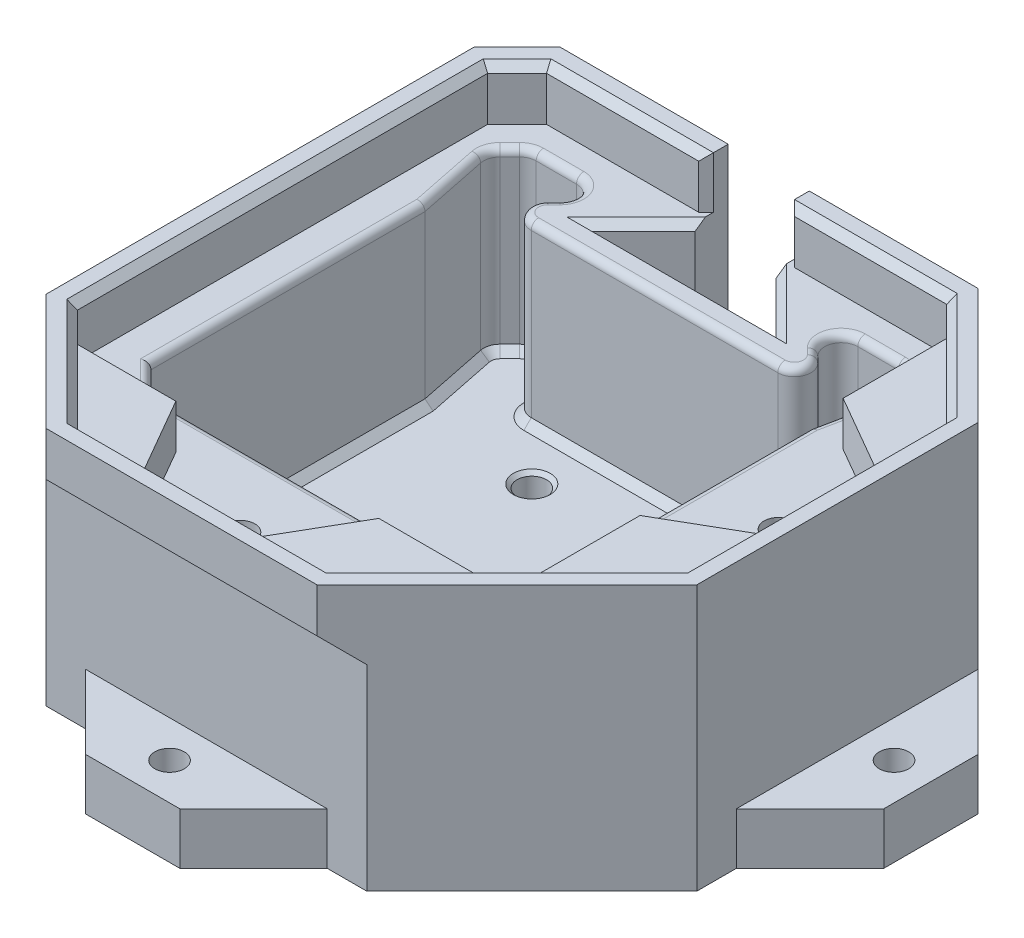
SolidWorks part; units mm, degrees
ref_plane "Front Plane" through (0, 0, 0) normal (0, 0, 1) x (1, 0, 0)
ref_plane "Top Plane" through (0, 0, 0) normal (0, 1, 0) x (1, 0, 0)
ref_plane "Right Plane" through (0, 0, 0) normal (1, 0, 0) x (0, 0, -1)
sketch "Sketch2" plane through (0, 0, 0) normal (0, 1, 0) x (1, 0, 0)
  line L0 (17.15, -41.8374) -> (-17.15, -41.8374)
  line L1 (41.15, -17.8374) -> (41.15, 17.8374)
  line L2 (27.15, 31.8374) -> (-27.15, 31.8374)
  line L3 (-31.15, -27.8374) -> (-31.15, 27.8374)
  line L4 (-17.15, -41.8374) -> (-31.15, -27.8374)
  line L5 (41.15, -17.8374) -> (17.15, -41.8374)
  line L6 (-27.15, 31.8374) -> (-31.15, 27.8374)
  line L7 (41.15, 17.8374) -> (27.15, 31.8374)
  point P0 (41.15, -41.8374)
  point P1 (-31.15, 31.8374)
  point P2 (41.15, 31.8374)
  point P3 (-31.15, -41.8374)
  point P15 (0, 31.8374)
  point P17 (41.15, 0)
  dimension "D1" = 73.6748
  dimension "D2" = 72.3
  dimension "D3" = 14
  dimension "D4" = 14
  dimension "D5" = 24
  dimension "D6" = 24
  dimension "D7" = 4
  dimension "D8" = 4
  dimension "D9" = 14
  dimension "D10" = 14
extrude "Boss-Extrude1" add sketch "Sketch2" along normal blind 6 and the other way blind 29
sketch "Sketch3" plane through (0, 6, 0) normal (0, 1, 0) x (1, 0, 0)
  line L5 (-8, -41.8374) -> (-13.7735, -31.8374)
  line L6 (-17.15, -41.8374) -> (17.15, -41.8374) construction
  line L7 (-13.7735, -31.8374) -> (13.7735, -31.8374)
  line L8 (13.7735, -31.8374) -> (8, -41.8374)
  line L9 (8, -41.8374) -> (-8, -41.8374)
  line L10 (41.15, -8) -> (41.15, 8)
  line L11 (41.15, -17.8374) -> (41.15, 17.8374) construction
  line L12 (41.15, 8) -> (31.15, 13.7735)
  line L13 (31.15, 13.7735) -> (31.15, -13.7735)
  line L14 (31.15, -13.7735) -> (41.15, -8)
  point P14 (0, -31.8374)
  point P21 (31.15, 0)
  dimension "D4" = 60
  dimension "D5" = 60
  dimension "D6" = 10
  dimension "D7" = 16
  dimension "D9" = 60
  dimension "D10" = 60
  dimension "D11" = 16
  dimension "D12" = 10
extrude "Cut-Extrude1" cut sketch "Sketch3" against normal blind 6
sketch "Sketch4" plane through (0, 6, 0) normal (0, 1, 0) x (1, 0, 0)
  line L0 (27.15, 31.8374) -> (-27.15, 31.8374) construction
  line L1 (-5.5, 31.8374) -> (5.5, 31.8374)
  line L2 (-5.5, 31.8374) -> (-5.5, 30.3374)
  line L3 (-5.5, 30.3374) -> (5.5, 30.3374) construction
  line L4 (5.5, 31.8374) -> (5.5, 30.3374)
  line L5 (-5.5, 30.3374) -> (-12.5, 23.3374)
  line L6 (-11.5, 24.3374) -> (11.5, 24.3374) construction
  line L7 (-12.5, 23.3374) -> (12.5, 23.3374)
  line L8 (12.5, 23.3374) -> (5.5, 30.3374)
  point P6 (0, 30.3374)
  dimension "D1" = 45
  dimension "D2" = 11
  dimension "D3" = 1.5
  dimension "D4" = 45
  dimension "D5" = 23
  dimension "D6" = 1
extrude "Cut-Extrude2" cut sketch "Sketch4" against normal through all both and the other way through all
sketch "Sketch5" plane through (0, 0, 0) normal (0, 1, 0) x (1, 0, 0)
  line L1 (-8, -41.8374) -> (8, -41.8374) construction
  line L2 (41.15, -8) -> (41.15, 8) construction
  circle A0 centre (36.15, 0) radius 1.95
  circle A1 centre (0, -36.8374) radius 1.95
  dimension "D1" = 3.9
  dimension "D2" = 3.9
  dimension "D3" = 5
  dimension "D4" = 5
extrude "Cut-Extrude3" cut sketch "Sketch5" against normal blind 12
sketch "Sketch6" plane through (0, 6, 0) normal (0, 1, 0) x (1, 0, 0)
  line L1 (31.15, 31.8374) -> (-31.15, 31.8374)
  line L2 (31.15, 31.8374) -> (31.15, -31.8374)
  line L3 (31.15, -31.8374) -> (-31.15, -31.8374)
  line L4 (-31.15, 31.8374) -> (-31.15, -31.8374)
  line L5 (13.7735, -31.8374) -> (-13.7735, -31.8374) construction
  line L7 (-5.5, 31.8374) -> (-27.15, 31.8374) construction
  line L8 (31.15, 13.7735) -> (31.15, -13.7735) construction
  line L9 (-31.15, 27.8374) -> (-31.15, -27.8374) construction
extrude "Cut-Extrude4" cut sketch "Sketch6" against normal blind 6
sketch "Sketch7" plane through (0, 0, 0) normal (0, 1, 0) x (1, 0, 0)
  line L5 (-22.15, 18.3374) -> (22.15, 18.3374) construction
  line L6 (-26.15, 14.3374) -> (-26.15, -22.8374)
  line L7 (-22.15, -26.8374) -> (22.15, -26.8374)
  line L8 (26.15, 14.3374) -> (26.15, -22.8374)
  line L9 (-27.15, -31.8374) -> (-13.7735, -31.8374) construction
  line L12 (-26.15, 14.3374) -> (-22.15, 18.3374) construction
  line L13 (-26.15, -22.8374) -> (-22.15, -26.8374)
  line L14 (22.15, -26.8374) -> (26.15, -22.8374)
  line L15 (22.15, 18.3374) -> (26.15, 14.3374) construction
  line L16 (31.15, -27.8374) -> (31.15, -13.7735) construction
  line L17 (-31.15, 27.8374) -> (-31.15, -27.8374) construction
  line L19 (-12.5, 23.3374) -> (12.5, 23.3374) construction
  line L80 (-26.15, 14.3374) -> (-28.3216, 25.009)
  line L81 (26.15, 14.3374) -> (28.3216, 25.009)
  line L89 (28.3216, 25.009) -> (25.4931, 27.8374)
  line L90 (25.4931, 27.8374) -> (13.6569, 27.8374)
  line L91 (-25.4931, 27.8374) -> (-28.3216, 25.009)
  line L92 (-13.6569, 27.8374) -> (-25.4931, 27.8374)
  line L93 (13.6569, 27.8374) -> (22.1569, 19.3374)
  line L94 (22.1569, 19.3374) -> (-22.1569, 19.3374)
  line L95 (-22.1569, 19.3374) -> (-13.6569, 27.8374)
  line L96 (28.3216, 25.009) -> (25.4931, 27.8374)
  line L97 (25.4931, 27.8374) -> (13.6569, 27.8374)
  line L98 (-25.4931, 27.8374) -> (-28.3216, 25.009)
  line L99 (-13.6569, 27.8374) -> (-25.4931, 27.8374)
  line L100 (13.6569, 27.8374) -> (22.1569, 19.3374)
  line L101 (22.1569, 19.3374) -> (-22.1569, 19.3374)
  line L102 (-22.1569, 19.3374) -> (-13.6569, 27.8374)
  point P0 (-26.15, 18.3374)
  point P1 (26.15, -26.8374)
  point P2 (-26.15, -26.8374)
  point P3 (26.15, 18.3374)
  dimension "D2" = 5
  dimension "D3" = 5
  dimension "D4" = 5
  dimension "D5" = 5
  dimension "D6" = 4
extrude "Cut-Extrude5" cut sketch "Sketch7" against normal offset from surface (24 mm away) 5 up to face at (1.4286, -29, -10.7875)
sketch "Sketch8" plane through (0, -29, 0) normal (0, -1, 0) x (1, 0, 0)
  line L5 (28.3926, -34.8374) -> (44.15, -19.08)
  line L6 (44.15, -19.08) -> (44.15, 19.08)
  line L7 (44.15, 19.08) -> (18.3926, 44.8374)
  line L8 (18.3926, 44.8374) -> (-18.3926, 44.8374)
  line L9 (-18.3926, 44.8374) -> (-34.15, 29.08)
  line L10 (-34.15, 29.08) -> (-34.15, -29.08)
  line L11 (-34.15, -29.08) -> (-28.3926, -34.8374)
  line L12 (-27.15, -31.8374) -> (-5.5, -31.8374)
  line L13 (-5.5, -31.8374) -> (-5.5, -30.3374)
  line L15 (5.5, -30.3374) -> (5.5, -31.8374)
  line L16 (5.5, -31.8374) -> (27.15, -31.8374)
  line L17 (27.15, -31.8374) -> (41.15, -17.8374)
  line L18 (41.15, -17.8374) -> (41.15, 17.8374)
  line L19 (41.15, 17.8374) -> (17.15, 41.8374)
  line L20 (17.15, 41.8374) -> (-17.15, 41.8374)
  line L21 (-17.15, 41.8374) -> (-31.15, 27.8374)
  line L22 (-31.15, 27.8374) -> (-31.15, -27.8374)
  line L23 (-31.15, -27.8374) -> (-27.15, -31.8374)
  line L24 (-27.15, -31.8374) -> (-5.5, -31.8374)
  line L28 (5.5, -31.8374) -> (27.15, -31.8374)
  line L29 (27.15, -31.8374) -> (41.15, -17.8374)
  line L30 (41.15, -17.8374) -> (41.15, 17.8374)
  line L31 (41.15, 17.8374) -> (17.15, 41.8374)
  line L32 (17.15, 41.8374) -> (-17.15, 41.8374)
  line L33 (-17.15, 41.8374) -> (-31.15, 27.8374)
  line L34 (-31.15, 27.8374) -> (-31.15, -27.8374)
  line L35 (-31.15, -27.8374) -> (-27.15, -31.8374)
  line L36 (-28.3926, -34.8374) -> (-5.5, -34.8374)
  line L37 (-5.5, -34.8374) -> (-5.5, -31.8374)
  line L38 (28.3926, -34.8374) -> (5.5, -34.8374)
  line L39 (5.5, -34.8374) -> (5.5, -31.8374)
  line L50 (-5.5, -30.3374) -> (5.5, -30.3374) construction
  line L56 (-2.5, -34.8374) -> (-2.5, -33.3374) construction
  line L57 (-5.5, -31.8374) -> (-5.5, -30.3374) construction
  line L58 (-2.5, -33.3374) -> (2.5, -33.3374) construction
  line L59 (5.5, -30.3374) -> (5.5, -31.8374) construction
  line L60 (2.5, -33.3374) -> (2.5, -34.8374) construction
  line L61 (2.5, -34.8374) -> (28.3926, -34.8374) construction
  line L62 (-28.3926, -34.8374) -> (-2.5, -34.8374) construction
  line L65 (-12.5, -23.3374) -> (12.5, -23.3374)
  line L66 (-5.5, -30.3374) -> (-12.5, -23.3374)
  line L69 (12.5, -23.3374) -> (5.5, -30.3374)
  dimension "D1" = 0
  dimension "D2" = 3
extrude "Boss-Extrude2" add sketch "Sketch8" against normal blind 36
chamfer "Chamfer1" distance 1 angle 45 9 edges at (-16.325, 7, -31.8374) (16.325, 7, -31.8374) (34.15, 7, -24.8374) (41.15, 7, 0) (29.15, 7, 29.8374) (0, 7, 41.8374) (-24.15, 7, 34.8374) (-31.15, 7, 0) (-29.15, 7, -29.8374)
fillet "Fillet2" radius 2.25 8 edges at (13.6569, -12, -27.8374) (-13.6569, -12, -27.8374) (22.1569, -12, -19.3374) (-22.1569, -12, -19.3374) (28.3216, -12, -25.009) (25.4931, -12, -27.8374) (-28.3216, -12, -25.009) (-25.4931, -12, -27.8374)
fillet "Fillet1" radius 1 22 edges at (-24.15, 0, 24.8374) (0, 0, 26.8374) (24.15, 0, 24.8374) (26.15, 0, 4.25) (-26.15, 0, 4.25) (-21.825, 0, -27.8374) (-26.8094, 0, -26.5211) (-27.1152, 0, -19.0808) (-17.9069, 0, -23.5874) (0, 0, -19.3374) (17.9069, 0, -23.5874) (21.825, 0, -27.8374) (26.8094, 0, -26.5211) (27.1152, 0, -19.0808) (-28.0302, 0, -24.9213) (-25.4222, 0, -27.6661) (-17.0101, 0, -26.4484) (-18.8036, 0, -20.7264) (18.8036, 0, -20.7264) (17.0101, 0, -26.4484) (25.4222, 0, -27.6661) (28.0302, 0, -24.9213)
chamfer "Chamfer3" distance 1 angle 45 22 edges at (26.15, -24, 4.25) (24.15, -24, 24.8374) (0, -24, 26.8374) (-24.15, -24, 24.8374) (-26.15, -24, 4.25) (-26.8094, -24, -26.5211) (-21.825, -24, -27.8374) (-17.9069, -24, -23.5874) (0, -24, -19.3374) (17.9069, -24, -23.5874) (21.825, -24, -27.8374) (26.8094, -24, -26.5211) (27.1152, -24, -19.0808) (-27.1152, -24, -19.0808) (-28.0302, -24, -24.9213) (-25.4222, -24, -27.6661) (-17.0101, -24, -26.4484) (-18.8036, -24, -20.7264) (18.8036, -24, -20.7264) (17.0101, -24, -26.4484) (25.4222, -24, -27.6661) (28.0302, -24, -24.9213)
chamfer "Chamfer5" distance 1 angle 45 5 edges at (5.5, 3, -31.8374) (-5.5, 3, -31.8374) (9, 0, -26.8374) (0, 0, -23.3374) (-9, 0, -26.8374)
sketch "Sketch10" plane through (0, -24, 0) normal (0, 1, 0) x (1, 0, 0)
  line L1 (-9.8995, -7.2121) -> (9.8995, -7.2121) construction
  line L2 (-9.8995, -7.2121) -> (-9.8995, 12.5869) construction
  line L3 (-9.8995, 12.5869) -> (9.8995, 12.5869) construction
  line L4 (9.8995, -7.2121) -> (9.8995, 12.5869) construction
  line L5 (-9.8995, -7.2121) -> (9.8995, 12.5869) construction
  line L6 (-9.8995, 12.5869) -> (9.8995, -7.2121) construction
  circle A0 centre (0, 2.6874) radius 14 construction
  circle A1 centre (-9.8995, 12.5869) radius 2
  circle A2 centre (9.8995, 12.5869) radius 2
  circle A3 centre (-9.8995, -7.2121) radius 2
  circle A4 centre (9.8995, -7.2121) radius 2
  dimension "D1" = 28
  dimension "D2" = 4
  dimension "D3" = 4
  dimension "D4" = 4
  dimension "D5" = 4
extrude "Cut-Extrude6" cut sketch "Sketch10" against normal through all
chamfer "Chamfer7" distance 0.5 angle 45 4 edges at (9.8995, -24, 9.2121) (-9.8995, -24, 9.2121) (9.8995, -24, -10.5869) (-9.8995, -24, -10.5869)
sketch "Sketch12" plane through (0, -29, 0) normal (0, -1, 0) x (1, 0, 0)
  line L0 (-999.7733, -2.6874) -> (49000.2267, -2.6874) construction
  line L2 (0, -1002.6874) -> (0, 48997.3126) construction
  line L3 (44.15, -19.08) -> (54.15, -9.08)
  line L4 (54.15, -9.08) -> (54.15, 3.7052)
  line L5 (54.15, 3.7052) -> (44.15, 13.7052)
  line L6 (44.15, -19.08) -> (44.15, 19.08) construction
  line L7 (44.15, -19.08) -> (44.15, 13.7052)
  line L8 (-34.15, -19.08) -> (-44.15, -19.08)
  line L9 (-34.15, 29.08) -> (-34.15, -29.08) construction
  line L10 (-44.15, -19.08) -> (-54.15, -9.08)
  line L11 (-54.15, -9.08) -> (-54.15, 3.7052)
  line L12 (-54.15, 3.7052) -> (-44.15, 13.7052)
  line L13 (-44.15, 13.7052) -> (-34.15, 13.7052)
  line L14 (-34.15, 13.7052) -> (-34.15, -19.08)
  circle A0 centre (-49.15, -2.6874) radius 2
  circle A1 centre (49.15, -2.6874) radius 2
  point P12 (54.15, -2.6874)
  dimension "D9" = 4
  dimension "D12" = 4
  dimension "D1" = 45
  dimension "D2" = 45
  dimension "D3" = 10
  dimension "D4" = 44.15
  dimension "D5" = 45
  dimension "D6" = 45
  dimension "D7" = 44.15
  dimension "D8" = 10
  dimension "D10" = 5
  dimension "D11" = 5
extrude "Boss-Extrude3" add sketch "Sketch12" against normal blind 7
sketch "Sketch13" plane through (0, -29, 0) normal (0, -1, 0) x (1, 0, 0)
  line L0 (-1000, -2.6874) -> (49000, -2.6874) construction
  line L1 (-9.8995, -12.5869) -> (9.8995, 7.2121) construction
  line L2 (0, -1002.6874) -> (0, 48997.3126) construction
  line L3 (-6.3926, 51.4626) -> (6.3926, 51.4626)
  line L4 (-6.3926, 51.4626) -> (-16.3926, 41.4626)
  line L5 (-16.3926, 41.4626) -> (16.3926, 41.4626)
  line L6 (16.3926, 41.4626) -> (6.3926, 51.4626)
  line L10 (-34.15, 13.7052) -> (-34.15, -19.08) construction
  circle A0 centre (0, 46.4626) radius 2
  point P5 (0, -2.6874)
  point P10 (0, 51.4626)
  dimension "D5" = 4
  dimension "D1" = 10
  dimension "D2" = 45
  dimension "D3" = 45
  dimension "D4" = 44.15
  dimension "D6" = 5
sketch "Sketch14" plane through (0, -29, 0) normal (0, -1, 0) x (1, 0, 0)
  line L1 (-16.3926, 41.4626) -> (16.3926, 41.4626)
  line L3 (18.3926, 44.8374) -> (-18.3926, 44.8374)
  line L4 (-16.3926, 41.4626) -> (-21.7674, 41.4626)
  line L5 (-18.3926, 44.8374) -> (-34.15, 29.08) construction
  line L6 (-21.7674, 41.4626) -> (-18.3926, 44.8374)
  line L7 (16.3926, 41.4626) -> (21.7674, 41.4626)
  line L8 (44.15, 19.08) -> (18.3926, 44.8374) construction
  line L9 (21.7674, 41.4626) -> (18.3926, 44.8374)
extrude "Cut-Extrude7" cut sketch "Sketch14" against normal blind 20
extrude "Boss-Extrude4" add sketch "Sketch13" against normal blind 7
chamfer "Chamfer8" distance 10 angle 45 1 edges at (0, -9, 44.8374)
sketch "Sketch15" plane through (0, -29, 0) normal (0, -1, 0) x (1, 0, 0)
  line L1 (-45.7, -0.6955) -> (-49.15, 1.2963)
  line L2 (-49.15, 1.2963) -> (-52.6, -0.6955)
  line L3 (-52.6, -0.6955) -> (-52.6, -4.6793)
  line L4 (-52.6, -4.6793) -> (-49.15, -6.6711)
  line L5 (-49.15, -6.6711) -> (-45.7, -4.6793)
  line L6 (-45.7, -4.6793) -> (-45.7, -0.6955)
  line L7 (0, 50.4463) -> (-3.45, 48.4545)
  line L8 (-3.45, 48.4545) -> (-3.45, 44.4707)
  line L9 (-3.45, 44.4707) -> (0, 42.4789)
  line L10 (0, 42.4789) -> (3.45, 44.4707)
  line L11 (3.45, 44.4707) -> (3.45, 48.4545)
  line L12 (3.45, 48.4545) -> (0, 50.4463)
  line L13 (49.15, 1.2963) -> (45.7, -0.6955)
  line L14 (45.7, -0.6955) -> (45.7, -4.6793)
  line L15 (45.7, -4.6793) -> (49.15, -6.6711)
  line L16 (49.15, -6.6711) -> (52.6, -4.6793)
  line L17 (52.6, -4.6793) -> (52.6, -0.6955)
  line L18 (52.6, -0.6955) -> (49.15, 1.2963)
  circle A0 centre (-49.15, -2.6874) radius 3.45 construction
  circle A1 centre (0, 46.4626) radius 3.45 construction
  circle A2 centre (49.15, -2.6874) radius 3.45 construction
  dimension "D1" = 6.9
  dimension "D2" = 6.9
  dimension "D3" = 6.9
extrude "Cut-Extrude8" cut sketch "Sketch15" against normal blind 4
